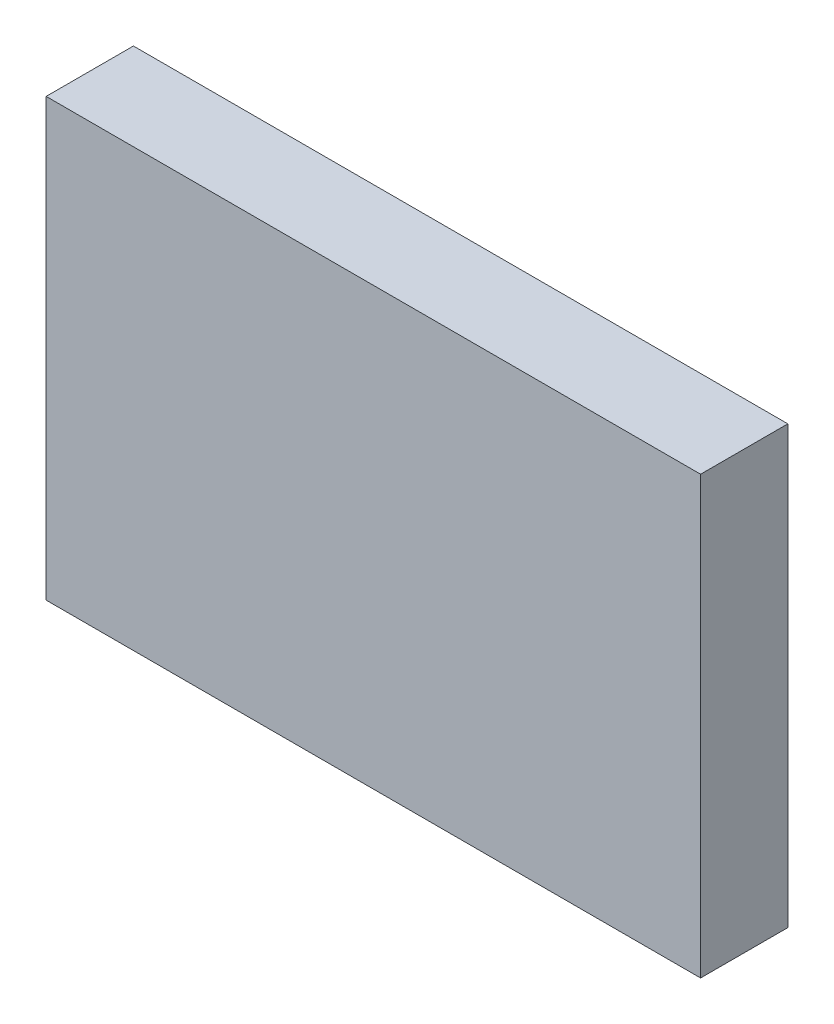
SolidWorks part; units mm, degrees
material "Лист 4,0 ГОСТ 19903-2015 / Ст3сп ГОСТ 14637-89"
ref_plane "Спереди" through (0, 0, 0) normal (0, 0, 1) x (1, 0, 0)
ref_plane "Сверху" through (0, 0, 0) normal (0, 1, 0) x (1, 0, 0)
ref_plane "Справа" through (0, 0, 0) normal (1, 0, 0) x (0, 0, -1)
sketch "Эскиз1" plane through (0, 0, 0) normal (0, 0, 1) x (1, 0, 0)
  line L1 (-15, -10) -> (15, -10)
  line L2 (-15, -10) -> (-15, 10)
  line L3 (-15, 10) -> (15, 10)
  line L4 (15, -10) -> (15, 10)
base flange "Базовая кромка1" sketch "Эскиз1" thickness 4 reverse thickness direction no parameters "D1"=4
sketch "Сгиб-Линии1" [suppressed] plane through (0, 0, 0) normal (0, 1, 0) x (1, 0, 0)
sketch "Граничная рамка1" [suppressed] plane through (0, 0, 0) normal (0, 1, 0) x (1, 0, 0)
sheet metal parameters "Листовой металл30" thickness 4 parameters "D1"=4
flat pattern "Развертка30" [suppressed]
sketch "Сгиб-Линии2" plane through (0, 0, 0) normal (0, 1, 0) x (1, 0, 0)
sketch3d "Граничная рамка2" [suppressed]
  line L0 (15, -10, 0) -> (-15, -10, 0) construction
  line L1 (15, 10, 0) -> (-15, 10, 0) construction
  line L2 (15, -10, 0) -> (15, 10, 0) construction
  line L3 (-15, -10, 0) -> (-15, 10, 0) construction
